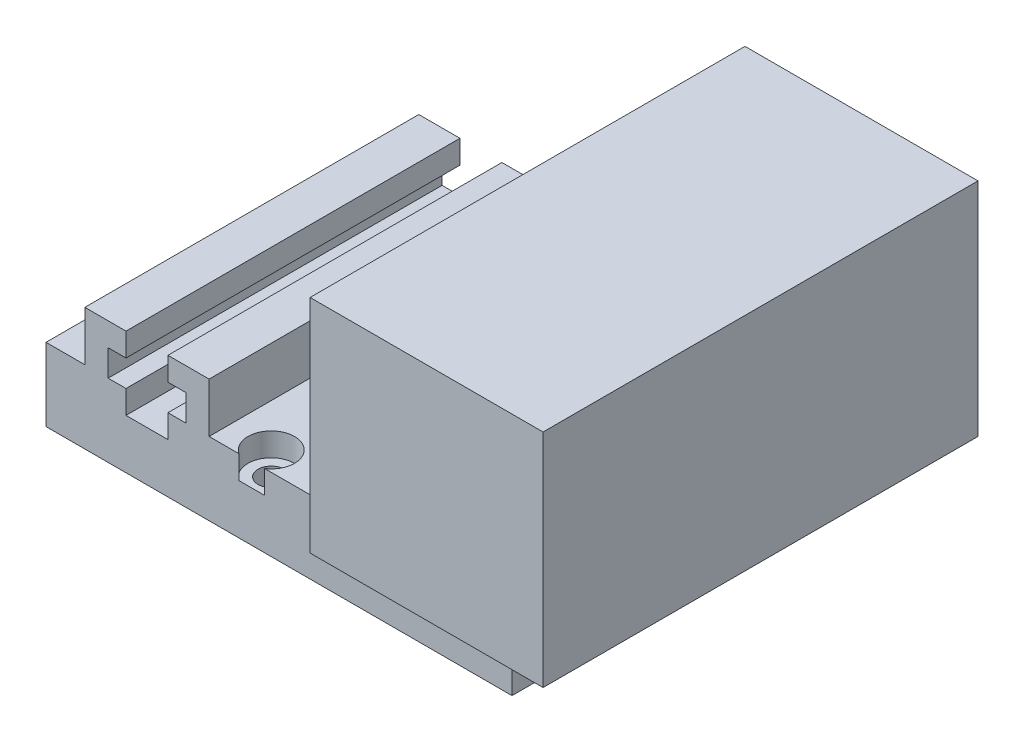
SolidWorks part; units mm, degrees
ref_plane "Front Plane" through (0, 0, 0) normal (0, 0, 1) x (1, 0, 0)
ref_plane "Top Plane" through (0, 0, 0) normal (0, 1, 0) x (1, 0, 0)
ref_plane "Right Plane" through (0, 0, 0) normal (1, 0, 0) x (0, 0, -1)
sketch "Sketch1" plane through (0, 0, 0) normal (0, 1, 0) x (1, 0, 0)
  line L1 (0, 0) -> (60, 0)
  line L2 (0, 0) -> (0, 43)
  line L3 (0, 43) -> (60, 43)
  line L4 (60, 0) -> (60, 43)
  dimension "D1" = 60
  dimension "D2" = 43
extrude "Boss-Extrude1" add sketch "Sketch1" along normal blind 5
sketch "Sketch2" plane through (0, 0, 0) normal (0, -1, 0) x (-1, 0, 0)
  line L0 (-60, 0) -> (-60, 43) construction
  line L1 (0, 0) -> (-60, 0)
  line L2 (0, 0) -> (0, 5)
  line L3 (0, 5) -> (-60, 5)
  line L4 (-60, 0) -> (-60, 5)
  line L6 (0, 43) -> (0, 0) construction
  line L7 (0, 43) -> (-60, 43)
  line L8 (0, 43) -> (0, 38)
  line L9 (0, 38) -> (-60, 38)
  line L10 (-60, 43) -> (-60, 38)
  dimension "D1" = 5
extrude "Boss-Extrude2" add sketch "Sketch2" along normal blind 4.4
sketch "Sketch3" plane through (0, 5, 0) normal (0, 1, 0) x (1, 0, 0)
  line L0 (60, 43) -> (0, 43) construction
  line L1 (5, 43) -> (8, 43)
  line L2 (5, 43) -> (5, 0)
  line L3 (5, 0) -> (8, 0)
  line L4 (8, 43) -> (8, 0)
  line L5 (0, 0) -> (60, 0) construction
  line L6 (0, 43) -> (0, 0) construction
  line L7 (18, 43) -> (21, 43)
  line L8 (18, 43) -> (18, 0)
  line L9 (18, 0) -> (21, 0)
  line L10 (21, 43) -> (21, 0)
  dimension "D1" = 3
  dimension "D2" = 10
  dimension "D3" = 5
extrude "Boss-Extrude3" add sketch "Sketch3" along normal blind 6.4
sketch "Sketch4" plane through (8, 0, 0) normal (1, 0, 0) x (0, 0, -1)
  line L0 (43, 11.4) -> (43, 5) construction
  line L1 (0, 11.4) -> (43, 11.4)
  line L2 (0, 11.4) -> (0, 8.4)
  line L3 (0, 8.4) -> (43, 8.4)
  line L4 (43, 11.4) -> (43, 8.4)
  dimension "D1" = 3
extrude "Boss-Extrude4" add sketch "Sketch4" along normal blind 2.3
ref_plane "Plane1" through (13, 0, 0) normal (1, 0, 0) x (0, 0, -1)
mirror "Mirror1" about plane through (13, 0, 0) normal (1, 0, 0) of "Boss-Extrude4"
sketch "Sketch5" plane through (0, 5, 0) normal (0, 1, 0) x (1, 0, 0)
  line L1 (40.5, 49.5) -> (70.5, 49.5)
  line L2 (40.5, 49.5) -> (40.5, -6.5)
  line L3 (40.5, -6.5) -> (70.5, -6.5)
  line L4 (70.5, 49.5) -> (70.5, -6.5)
  line L6 (13, -1.87) -> (13, 1.87) construction
  line L7 (60, 0) -> (60, 43) construction
  line L8 (60, 21.5) -> (70.5, 21.5) construction
  dimension "D1" = 30
  dimension "D2" = 27.5
  dimension "D3" = 56
extrude "Boss-Extrude5" add sketch "Sketch5" along normal blind 28.5
sketch "Sketch6" plane through (40.5, 0, 0) normal (-1, 0, 0) x (0, 0, 1)
  line L0 (-43, 5) -> (0, 5) construction
  line L1 (-41.7, 30.7) -> (-1.3, 30.7)
  line L2 (-41.7, 30.7) -> (-41.7, 10.3)
  line L3 (-41.7, 10.3) -> (-1.3, 10.3)
  line L4 (-1.3, 30.7) -> (-1.3, 10.3)
  line L5 (-49.5, 33.5) -> (6.5, 33.5) construction
  line L6 (-21.5, 30.7) -> (-21.5, 33.5) construction
  point P4 (-41.7, 20.5)
  dimension "D1" = 20.4
  dimension "D2" = 15.5
  dimension "D3" = 40.4
extrude "Cut-Extrude1" cut sketch "Sketch6" against normal blind 28
sketch "Sketch7" plane through (40.5, 0, 0) normal (-1, 0, 0) x (0, 0, 1)
  line L0 (-46, 25.5) -> (3, 25.5) construction
  line L1 (-49.5, 33.5) -> (6.5, 33.5) construction
  line L2 (-21.5, 25.5) -> (-21.5, 33.5) construction
  line L3 (3, 25.5) -> (3, 15.5)
  line L4 (3, 20.5) -> (-1.3, 20.5) construction
  line L5 (-1.3, 10.3) -> (-1.3, 30.7) construction
  circle A0 centre (-46, 25.5) radius 1.05
  circle A1 centre (-46, 15.5) radius 1.05
  circle A2 centre (3, 25.5) radius 1.05
  circle A3 centre (3, 15.5) radius 1.05
  dimension "D1" = 2.1
  dimension "D2" = 10
  dimension "D3" = 49
extrude "Cut-Extrude2" cut sketch "Sketch7" against normal blind 25 contours A0 | A1 | A3 | A2 region at (40.5, 16.2215, 3.7215) region at (40.5, 26.2215, 2.2785) region at (40.5, 25.5, -46) region at (40.5, 15.5, -46)
sketch "Sketch8" plane through (0, 0, 0) normal (0, 0, 1) x (1, 0, 0)
  line L0 (8, 5) -> (18, 5) construction
  line L1 (10.3, 5) -> (15.7, 5)
  line L2 (10.3, 5) -> (10.3, 2)
  line L3 (10.3, 2) -> (15.7, 2)
  line L4 (15.7, 5) -> (15.7, 2)
  line L5 (13, -1.87) -> (13, 1.87) construction
  point P6 (13, 5)
  dimension "D1" = 3
  dimension "D2" = 5.4
extrude "Cut-Extrude3" cut sketch "Sketch8" against normal offset from surface (33 mm away) 10 up to face at (18.6176, 6.2, -43)
sketch "Sketch9" plane through (0, 5, 0) normal (0, 1, 0) x (1, 0, 0)
  line L0 (40.5, 43) -> (21, 43) construction
  line L1 (40.5, 49.5) -> (40.5, -6.5) construction
  line L2 (0, 21.5) -> (50000, 21.5) construction
  line L3 (0, 43) -> (0, 0) construction
  circle A0 centre (26.5, 40.5) radius 1.7
  circle A1 centre (36.5, 40.5) radius 1.7
  circle A2 centre (36.5, 2.5) radius 1.7
  circle A3 centre (26.5, 2.5) radius 1.7
  point P12 (0, 21.5)
  dimension "D1" = 3.4
  dimension "D2" = 10
  dimension "D3" = 2.5
  dimension "D4" = 4
extrude "Cut-Extrude4" cut sketch "Sketch9" against normal up to next
sketch "Sketch10" plane through (0, 5, 0) normal (0, 1, 0) x (1, 0, 0)
  circle A0 centre (26.5, 40.5) radius 3
  circle A1 centre (36.5, 40.5) radius 3
  circle A2 centre (26.5, 2.5) radius 3
  circle A3 centre (36.5, 2.5) radius 3
  dimension "D1" = 6
extrude "Cut-Extrude5" cut sketch "Sketch10" against normal blind 3
